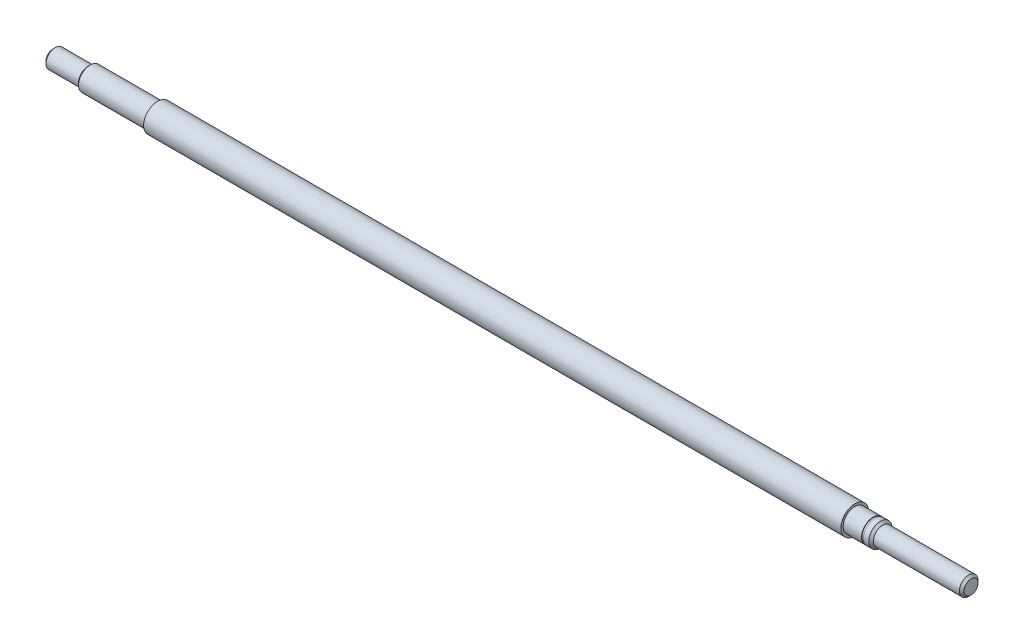
SolidWorks part; units mm, degrees
material "45 钢"
ref_plane "前视基准面" through (0, 0, 0) normal (0, 0, 1) x (1, 0, 0)
ref_plane "上视基准面" through (0, 0, 0) normal (0, 1, 0) x (1, 0, 0)
ref_plane "右视基准面" through (0, 0, 0) normal (1, 0, 0) x (0, 0, -1)
sketch "草图1" plane through (0, 0, 0) normal (0, 0, 1) x (1, 0, 0)
  line L0 (0, 0) -> (0, 4)
  line L1 (0, 4) -> (15, 4)
  line L2 (15, 4) -> (15, 5)
  line L3 (15, 5) -> (45, 5)
  line L4 (45, 5) -> (45, 6)
  line L5 (45, 6) -> (345, 6)
  line L6 (345, 6) -> (345, 5)
  line L7 (345, 5) -> (352.9, 5)
  line L8 (352.9, 5) -> (352.9, 4.8)
  line L9 (0, 0) -> (357, 0) construction
  line L10 (352.9, 4.8) -> (353.7, 4.8)
  line L11 (353.7, 4.8) -> (353.7, 5)
  line L12 (353.7, 5) -> (357, 5)
  line L13 (357, 5) -> (357, 0)
  line L14 (0, 0) -> (357, 0)
  line L16 (357, 4) -> (395, 4)
  line L17 (357, 4) -> (357, 0)
  line L18 (357, 0) -> (395, 0)
  line L19 (395, 4) -> (395, 0)
  line L20 (376, 0) -> (376, 4) construction
  line L21 (357, 2) -> (395, 2) construction
  point P107 (376, 2)
  dimension "D1" = 8
  dimension "D2" = 15
  dimension "D3" = 10
  dimension "D4" = 30
  dimension "D5" = 12
  dimension "D6" = 300
  dimension "D7" = 7.9
  dimension "D8" = 10
  dimension "D9" = 0.8
  dimension "D10" = 10
  dimension "D11" = 12
  dimension "D12" = 0.2
  dimension "D13" = 4
  dimension "D14" = 50
revolve "旋转1" add sketch "草图1" angle 360 about L9 region at (182.1172, 2.9201, 0) region at (376, 2, 0)
cosmetic thread "装饰螺纹线1" parameters "D2"=10.106
cosmetic thread "装饰螺纹线2" parameters "D1"=16, "D2"=8.376
chamfer "倒角1" distance 1 angle 45 4 edges at (395, 0, 4) (0, 0, 4) (15, 0, 5) (357, 0, 5)
